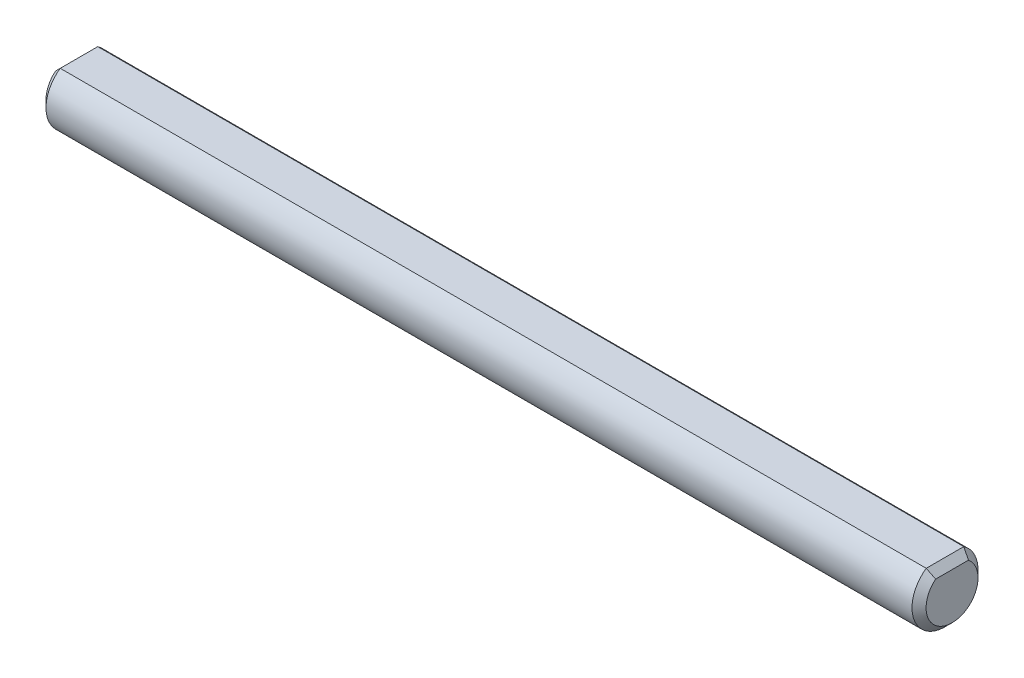
SolidWorks part; units mm, degrees
ref_plane "Front Plane" through (0, 0, 0) normal (0, 0, 1) x (1, 0, 0)
ref_plane "Top Plane" through (0, 0, 0) normal (0, 1, 0) x (1, 0, 0)
ref_plane "Right Plane" through (0, 0, 0) normal (1, 0, 0) x (0, 0, -1)
sketch "Sketch1" plane through (0, 0, 0) normal (1, 0, 0) x (0, 0, -1)
  line L1 (1.0667, 1.542) -> (-1.0667, 1.542)
  arc A0 (-1.0667, 1.542) -> (1.0667, 1.542) centre (0, 0) ccw
  dimension "D1" = 3.75
extrude "Boss-Extrude1" add sketch "Sketch1" along normal mid plane 50
chamfer "Chamfer1" distance 0.4 angle 45 4 edges at (-25, 1.542, 0) (-25, -1.875, 0) (25, 1.542, 0) (25, -1.875, 0)
